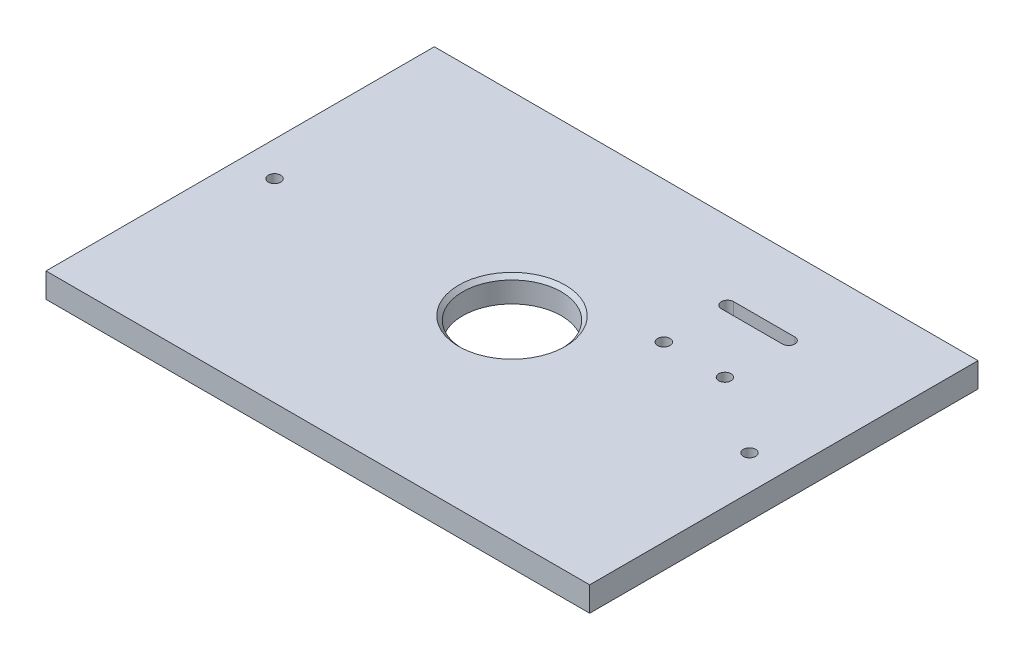
SolidWorks part; units mm, degrees
material "Oak"
ref_plane "Front Plane" through (0, 0, 0) normal (0, 0, 1) x (1, 0, 0)
ref_plane "Top Plane" through (0, 0, 0) normal (0, 1, 0) x (1, 0, 0)
ref_plane "Right Plane" through (0, 0, 0) normal (1, 0, 0) x (0, 0, -1)
sketch "Sketch1" plane through (0, 0, 0) normal (0, 1, 0) x (1, 0, 0)
  line L1 (0, 0) -> (140, 0)
  line L2 (0, 0) -> (0, 100)
  line L3 (0, 100) -> (140, 100)
  line L4 (140, 0) -> (140, 100)
  dimension "D1" = 140
  dimension "D2" = 100
extrude "Boss-Extrude1" add sketch "Sketch1" along normal blind 6.35
sketch "Sketch2" plane through (0, 6.35, 0) normal (0, 1, 0) x (1, 0, 0)
  line L0 (70, 100) -> (70, 0) construction
  line L1 (140, 100) -> (0, 100) construction
  line L2 (0, 0) -> (140, 0) construction
  line L3 (0, 50) -> (140, 50) construction
  line L4 (0, 100) -> (0, 0) construction
  line L5 (140, 0) -> (140, 100) construction
  circle A0 centre (70, 50) radius 12.705
  dimension "D1" = 25.41
extrude "Cut-Extrude1" cut sketch "Sketch2" against normal blind 10
sketch "Sketch3" plane through (0, 6.35, 0) normal (0, 1, 0) x (1, 0, 0)
  line L0 (0, 100) -> (0, 0) construction
  line L1 (140, 0) -> (140, 100) construction
  circle A0 centre (8.85, 50) radius 1.5875
  circle A1 centre (131.15, 50) radius 1.5875
  point P0 (0, 100)
  point P1 (0, 50)
  point P3 (8.85, 50)
  point P6 (131.15, 50)
  dimension "D1" = 3.175
  dimension "D2" = 3.175
  dimension "D3" = 8.85
  dimension "D4" = 8.85
extrude "Cut-Extrude2" cut sketch "Sketch3" against normal blind 10
chamfer "Chamfer1" distance 1 angle 45 1 edges at (70, 6.35, -37.295)
sketch "Sketch4" plane through (0, 6.35, 0) normal (0, 1, 0) x (1, 0, 0)
  line L0 (95.4, 81.6925) -> (111.13, 81.6925)
  line L1 (95.4, 78.5175) -> (111.13, 78.5175)
  circle A0 centre (95.4, 63.705) radius 1.5875
  circle A1 centre (111.13, 63.705) radius 1.5875
  circle A2 centre (111.13, 80.105) radius 1.5875
  circle A3 centre (95.4, 80.105) radius 1.5875
  circle A4 centre (70, 50) radius 13.705 construction
  point P9 (70, 63.705)
  dimension "D1" = 3.175
  dimension "D2" = 3.175
  dimension "D3" = 3.175
  dimension "D4" = 3.175
  dimension "D5" = 15.73
  dimension "D6" = 16.4
  dimension "D7" = 25.4
extrude "Cut-Extrude4" cut sketch "Sketch4" against normal blind 10 contours A3 L1 A2 L0 | A3 | A1 | A2 | A0 region at (103.265, 6.35, -80.105) region at (95.4, 6.35, -80.105) region at (111.13, 6.35, -63.705)
